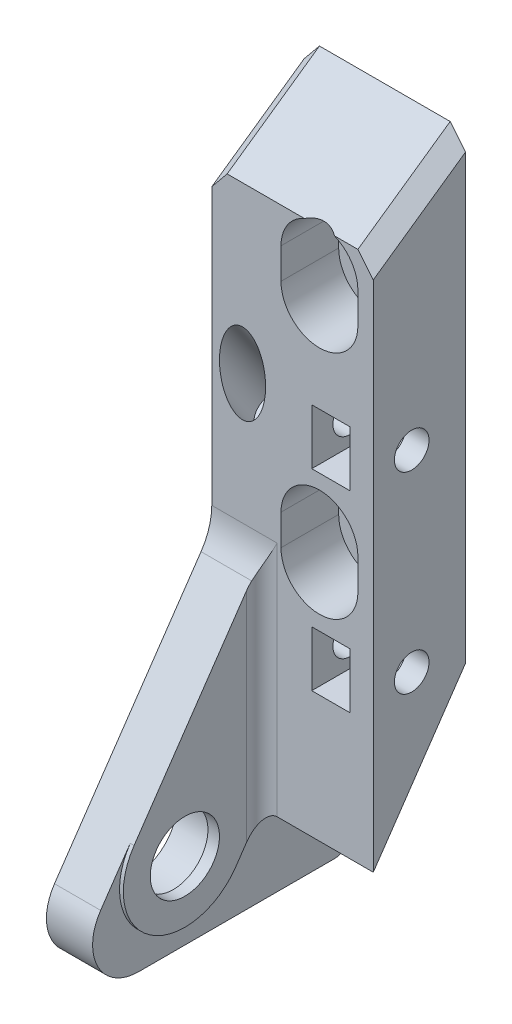
SolidWorks part; units mm, degrees
material "3D printed plastic"
ref_plane "Front Plane" through (0, 0, 0) normal (0, 0, 1) x (1, 0, 0)
ref_plane "Top Plane" through (0, 0, 0) normal (0, 1, 0) x (1, 0, 0)
ref_plane "Right Plane" through (0, 0, 0) normal (1, 0, 0) x (0, 0, -1)
sketch "Sketch1" plane through (0, 0, 0) normal (1, 0, 0) x (0, 0, -1)
  line L0 (22, 78) -> (22, 18)
  line L1 (6.6037, -4.5156) -> (22, 18)
  line L2 (10, 69.5975) -> (10, 28.797)
  line L4 (10, 28.797) -> (-6.6037, 4.5156)
  line L5 (22, 78) -> (10, 69.5975)
  circle A0 centre (0, 0) radius 4.5
  arc A1 (-6.6037, 4.5156) -> (6.6037, -4.5156) centre (0, 0) ccw
  dimension "D1" = 22
  dimension "D2" = 9
  dimension "D4" = 18
  dimension "D5" = 0
  dimension "D7" = 8
  dimension "D3" = 60
  dimension "D6" = 12
  dimension "D8" = 55
extrude "Boss-Extrude1" add sketch "Sketch1" along normal mid plane 21
sketch "Sketch2" plane through (0, 0, -10) normal (0, 0, 1) x (1, 0, 0)
  line L0 (3.5, 65) -> (3.5, 61) construction
  line L1 (5.75, 65) -> (5.75, 61)
  line L2 (1.25, 65) -> (1.25, 61)
  line L3 (3.5, 35) -> (3.5, 31) construction
  line L4 (5.75, 35) -> (5.75, 31)
  line L5 (1.25, 35) -> (1.25, 31)
  line L6 (3.5, 33) -> (3.5, 63) construction
  line L7 (3.5, 63) -> (3.5, 78) construction
  line L8 (10.5, 78) -> (-10.5, 78) construction
  line L10 (10.5, 78) -> (10.5, 69.5975) construction
  arc A0 (5.75, 65) -> (1.25, 65) centre (3.5, 65) ccw
  arc A1 (1.25, 61) -> (5.75, 61) centre (3.5, 61) ccw
  arc A2 (5.75, 35) -> (1.25, 35) centre (3.5, 35) ccw
  arc A3 (1.25, 31) -> (5.75, 31) centre (3.5, 31) ccw
  point P2 (3.5, 63)
  point P7 (3.5, 33)
  dimension "D1" = 30
  dimension "D2" = 4
  dimension "D3" = 4.5
  dimension "D4" = 15
  dimension "D5" = 7
extrude "Cut-Extrude1" cut sketch "Sketch2" against normal through all both and the other way through all
sketch "Sketch3" plane through (0, 0, -10) normal (0, 0, 1) x (1, 0, 0)
  line L0 (3.5, 65) -> (3.5, 61) construction
  line L1 (8.5, 65) -> (8.5, 61)
  line L2 (-1.5, 65) -> (-1.5, 61)
  line L3 (3.5, 35) -> (3.5, 31) construction
  line L4 (8.5, 35) -> (8.5, 31)
  line L5 (-1.5, 35) -> (-1.5, 31)
  arc A0 (8.5, 65) -> (-1.5, 65) centre (3.5, 65) ccw
  arc A1 (-1.5, 61) -> (8.5, 61) centre (3.5, 61) ccw
  arc A2 (8.5, 35) -> (-1.5, 35) centre (3.5, 35) ccw
  arc A3 (-1.5, 31) -> (8.5, 31) centre (3.5, 31) ccw
  point P4 (3.5, 63)
  point P9 (3.5, 33)
  dimension "D1" = 10
extrude "Cut-Extrude2" cut sketch "Sketch3" against normal blind 7.5 and the other way through all
sketch "Sketch4" plane through (-10.5, 0, 0) normal (-1, 0, 0) x (0, 0, 1)
  circle A0 centre (0, 0) radius 5.5
  dimension "D1" = 11
extrude "Cut-Extrude3" cut sketch "Sketch4" against normal blind 5
sketch "Sketch5" plane through (10.5, 0, 0) normal (1, 0, 0) x (0, 0, -1)
  line L0 (10, 28.797) -> (10, 0)
  line L1 (10, 28.797) -> (-3.217, 9.4684)
  line L2 (10, 28.797) -> (-6.6037, 4.5156) construction
  arc A0 (-3.217, 9.4684) -> (10, 0) centre (0, 0) ccw
  dimension "D1" = 20
extrude "Cut-Extrude4" cut sketch "Sketch5" against normal offset from surface (14.5 mm away) 6.5 up to face at (-10.5, 0, 5.5)
fillet "Fillet1" radius 2 1 edges at (-4, 14.6241, -10)
chamfer "Chamfer1" distance 2 angle 45 2 edges at (-10.5, 73.7988, -16) (10.5, 73.7988, -16)
ref_plane "Plane1" through (-6.5, 0, 0) normal (-1, 0, 0) x (0, 0, 1)
sketch "Sketch6" plane through (-6.5, 0, 0) normal (-1, 0, 0) x (0, 0, 1)
  line L0 (-22, 31) -> (-8.6484, 50.0681) construction
  line L1 (-22, 18) -> (-22, 75.5585) construction
  line L2 (-22, 31) -> (-23.3516, 29.0697) construction
  line L3 (-23.3516, 29.0697) -> (-22, 28.1233)
  line L4 (-22, 28.1233) -> (-7.2968, 49.1217)
  line L5 (-7.2968, 49.1217) -> (-8.6484, 50.0681)
  line L6 (-8.6484, 50.0681) -> (-10, 51.0145) construction
  line L7 (-10, 67.156) -> (-10, 28.797) construction
  line L8 (-8.6484, 50.0681) -> (-23.3516, 29.0697)
  dimension "D1" = 3.3
  dimension "D2" = 35
  dimension "D3" = 13
revolve "Cut-Revolve1" cut sketch "Sketch6" angle 360 about L8
ref_plane "Plane2" through (-6.5, 29.0697, -23.3516) normal (0, -0.8192, -0.5736) x (-1, 0, 0)
sketch "Sketch7" plane through (-6.5, 29.0697, -23.3516) normal (0, -0.8192, -0.5736) x (-1, 0, 0)
  line L1 (0, -3.1754) -> (2.75, -1.5877)
  line L2 (2.75, -1.5877) -> (2.75, 1.5877)
  line L3 (2.75, 1.5877) -> (0, 3.1754)
  line L4 (0, 3.1754) -> (-2.75, 1.5877)
  line L5 (-2.75, 1.5877) -> (-2.75, -1.5877)
  line L6 (-2.75, -1.5877) -> (0, -3.1754)
  circle A0 centre (0, 0) radius 2.75 construction
  dimension "D1" = 5.5
extrude "Cut-Extrude5" cut sketch "Sketch7" against normal blind 9 and the other way through all
sketch "Sketch8" plane through (0, 15.9068, 11.138) normal (0, -0.8192, -0.5736) x (1, 0, 0)
  circle A0 centre (-6.5, -35.8022) radius 3
  dimension "D1" = 6
extrude "Cut-Extrude6" cut sketch "Sketch8" against normal through all from offset 5 offset against normal yes
fillet "Fillet3" radius 8 1 edges at (-6.25, 28.797, -10)
hole_wizard "M4 Clearance Hole1" positions "Sketch10" profile "Sketch9" hole size "M4" standard "DIN"
sketch "Sketch10" plane through (10.5, 0, 0) normal (1, 0, 0) x (0, 0, -1)
  line L0 (15, 45.5) -> (15, 20.5) construction
  line L4 (15, 33) -> (10, 33) construction
  line L5 (10, 67.156) -> (10, 0.4511) construction
  circle A0 centre (0, 0) radius 4.5 construction
  point P0 (15, 45.5)
  point P2 (15, 20.5)
  dimension "D1" = 25
  dimension "D2" = 5
  dimension "D3" = 33
sketch "Sketch9" plane through (10.5, 45.5, -15) normal (0, 1, 0) x (0, 0, -1)
  line L0 (0, 0) -> (0, 13.3519)
  line L1 (0, 13.3519) -> (2.25, 12)
  line L2 (2.25, 12) -> (2.25, 0)
  line L5 (2.25, 0) -> (0, 0)
  line L10 (0, 13.3519) -> (-2.25, 12) construction
  line L11 (0, -6.35) -> (0, 107.95) construction
  dimension "Hole Dia." = 4.5
  dimension "Hole Depth" = 12
  dimension "Drill Angle" = 118
sketch "Sketch11" plane through (10.5, 0, 0) normal (1, 0, 0) x (0, 0, -1)
  line L0 (12.9215, 49.1) -> (7.9215, 49.1)
  line L1 (10.8431, 45.5) -> (12.9215, 41.9) construction
  line L2 (12.9215, 41.9) -> (17.0785, 41.9)
  line L3 (17.0785, 41.9) -> (19.1569, 45.5)
  line L4 (19.1569, 45.5) -> (17.0785, 49.1)
  line L5 (17.0785, 49.1) -> (12.9215, 49.1)
  line L6 (12.9215, 49.1) -> (10.8431, 45.5) construction
  line L7 (10.8431, 20.5) -> (12.9215, 16.9) construction
  line L8 (12.9215, 16.9) -> (17.0785, 16.9)
  line L9 (17.0785, 16.9) -> (19.1569, 20.5)
  line L10 (19.1569, 20.5) -> (17.0785, 24.1)
  line L11 (17.0785, 24.1) -> (12.9215, 24.1)
  line L12 (12.9215, 24.1) -> (10.8431, 20.5) construction
  line L13 (7.9215, 49.1) -> (7.9215, 41.9)
  line L14 (7.9215, 41.9) -> (12.9215, 41.9)
  line L16 (12.9215, 24.1) -> (7.9215, 24.1)
  line L17 (7.9215, 24.1) -> (7.9215, 16.9)
  line L18 (7.9215, 16.9) -> (12.9215, 16.9)
  circle A0 centre (15, 45.5) radius 3.6 construction
  circle A1 centre (15, 20.5) radius 3.6 construction
  dimension "D1" = 7.2
  dimension "D2" = 5
extrude "Cut-Extrude7" cut sketch "Sketch11" against normal blind 5 from offset 3 offset against normal yes
sketch "Sketch12" plane through (-10.5, 0, 0) normal (-1, 0, 0) x (0, 0, 1)
  line L0 (-19.9999, -10.5) -> (5.5, -10.5)
  line L1 (6.6037, 4.5156) -> (10.4528, -1.1133)
  line L2 (-8.6037, 26.7551) -> (6.6037, 4.5156) construction
  line L3 (-21.9999, -8.5) -> (-21.9999, 17.9999)
  line L4 (-6.6037, -4.5156) -> (-22, 18) construction
  line L5 (-21.9999, 17.9999) -> (-6.6037, -4.5156)
  line L6 (-22, 18) -> (-22, 75.5585) construction
  circle A0 centre (0, 0) radius 5.5 construction
  arc A1 (10.4528, -1.1133) -> (5.5, -10.5) centre (5.5, -4.5) cw
  arc A2 (-19.9999, -10.5) -> (-21.9999, -8.5) centre (-19.9999, -8.5) cw
  arc A4 (-6.6037, -4.5156) -> (6.6037, 4.5156) centre (0, 0) ccw
  dimension "D1" = 10.5
  dimension "D2" = 0.0001
  dimension "D3" = 6
  dimension "D4" = 2
extrude "Boss-Extrude2" add sketch "Sketch12" against normal blind 6
chamfer "Chamfer2" distance 4 angle 45 1 edges at (-10.5, 4.7499, -21.9999) tangent propagation no
